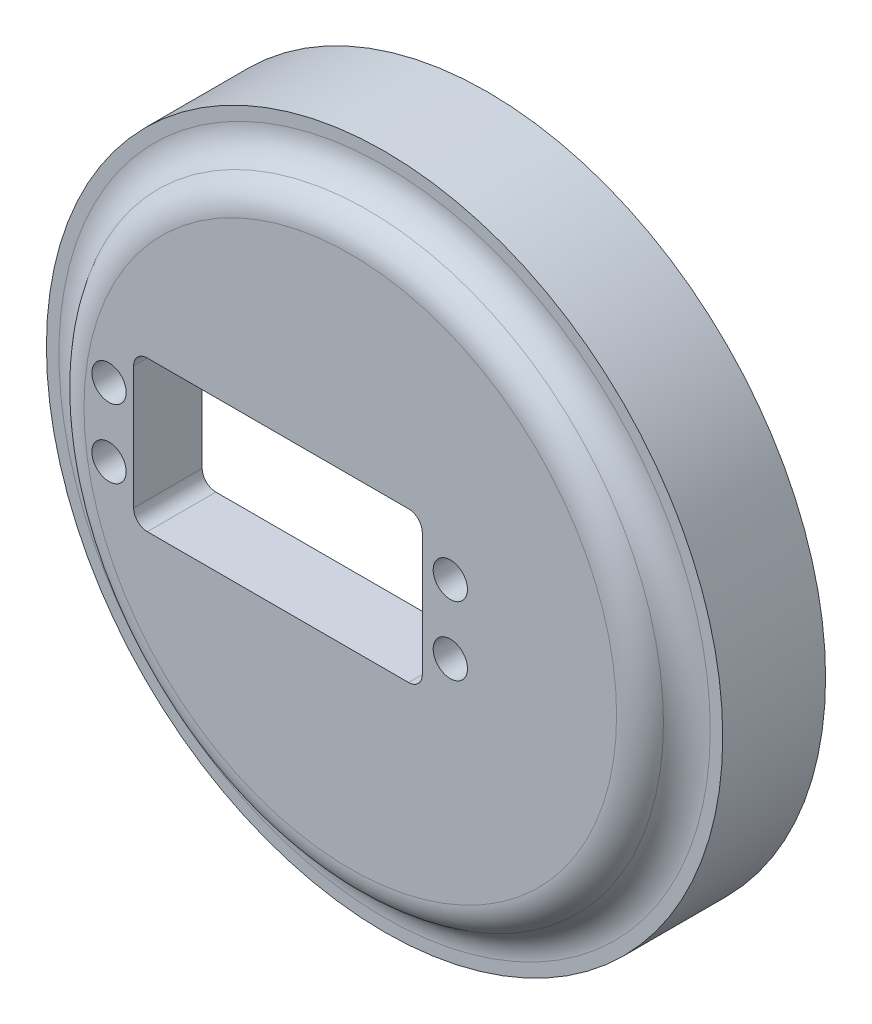
SolidWorks part; units mm, degrees
ref_plane "Front Plane" through (0, 0, 0) normal (0, 0, 1) x (1, 0, 0)
ref_plane "Top Plane" through (0, 0, 0) normal (0, 1, 0) x (1, 0, 0)
ref_plane "Right Plane" through (0, 0, 0) normal (1, 0, 0) x (0, 0, -1)
sketch "Sketch1" plane through (0, 0, 0) normal (0, 0, 1) x (1, 0, 0)
  circle A0 centre (0, 0) radius 46.32
  dimension "D1" = 92.64
extrude "Extrude-Thin1" add sketch "Sketch1" along normal blind 10 thin thin type one direction wall 3
sketch "Sketch2" plane through (0, 0, 10) normal (0, 0, 1) x (1, 0, 0)
  circle A1 centre (0, 0) radius 49.32
extrude "Boss-Extrude1" add sketch "Sketch2" along normal blind 5
sketch "Sketch3" plane through (0, 0, 15) normal (0, 0, 1) x (1, 0, 0)
  circle A0 centre (0, 0) radius 42.5
  dimension "D1" = 85
extrude "Boss-Extrude2" add sketch "Sketch3" along normal blind 5
fillet "Fillet1" radius 5 2 edges at (42.5, 0, 15) (46.32, 0, 10)
fillet "Fillet2" radius 5 1 edges at (42.5, 0, 20)
sketch "Sketch4" plane through (0, 0, 20) normal (0, 0, 1) x (1, 0, 0)
  line L1 (-31.6, 10.9) -> (10.5, 10.9)
  line L2 (-31.6, 10.9) -> (-31.6, -11.0348)
  line L3 (-31.6, -11.0348) -> (10.5, -11.0348)
  line L4 (10.5, 10.9) -> (10.5, -11.0348)
  line L5 (-31.6, 10.9) -> (10.5, -11.0348) construction
  line L6 (-31.6, -11.0348) -> (10.5, 10.9) construction
  circle A0 centre (-35.1896, 5) radius 2.5
  circle A1 centre (-35.1896, -5) radius 2.5
  circle A2 centre (14.5896, 5) radius 2.5
  circle A3 centre (14.5896, -5) radius 2.5
  circle A4 centre (0, 0) radius 38.8397 construction
  point P0 (-10.55, -0.0674)
  point P9 (0, 0)
  dimension "D1" = 49.7792
  dimension "D3" = 10
  dimension "D6" = 5
  dimension "D7" = 5
  dimension "D8" = 5
  dimension "D9" = 5
  dimension "D2" = 10.9
  dimension "D4" = 11.0348
  dimension "D5" = 42.1
extrude "Cut-Extrude1" cut sketch "Sketch4" against normal through all
fillet "Fillet3" radius 2 4 edges at (10.5, 10.9, 15) (10.5, -11.0348, 15) (-31.6, -11.0348, 15) (-31.6, 10.9, 15)
